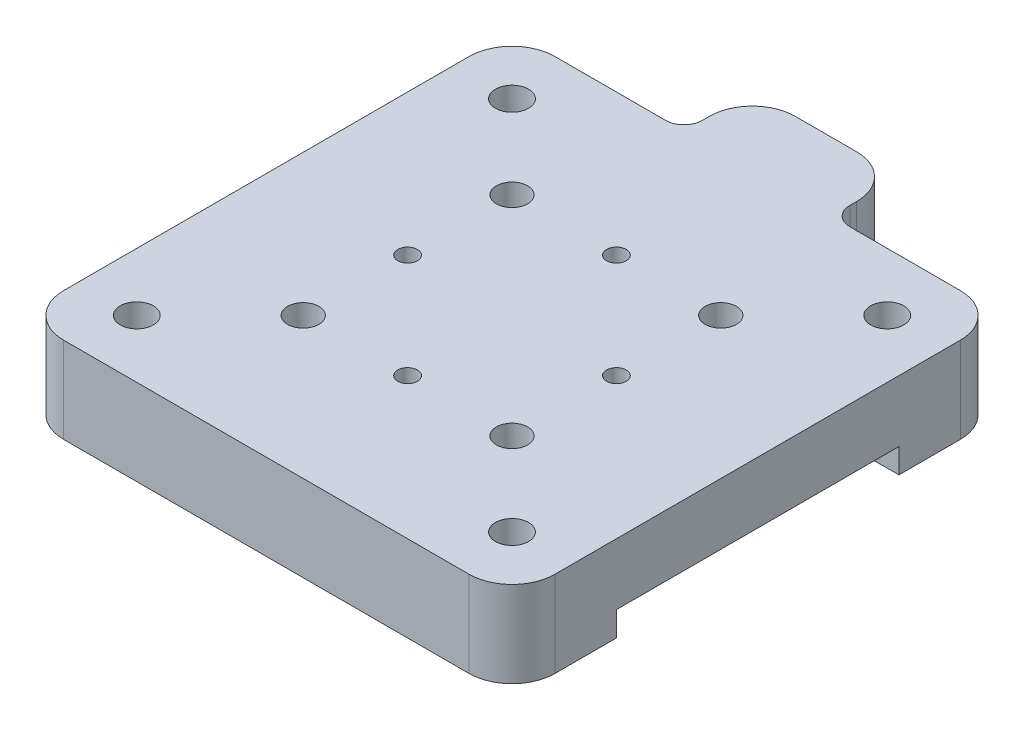
SolidWorks part; units mm, degrees
ref_plane "Front Plane" through (0, 0, 0) normal (0, 0, 1) x (1, 0, 0)
ref_plane "Top Plane" through (0, 0, 0) normal (0, 1, 0) x (1, 0, 0)
ref_plane "Right Plane" through (0, 0, 0) normal (1, 0, 0) x (0, 0, -1)
sketch "Sketch1" plane through (0, 0, 0) normal (0, 1, 0) x (1, 0, 0)
  line L3 (0, 40) -> (40, 40)
  line L4 (40, 0) -> (40, 40)
  line L5 (40, 40) -> (-40, 40)
  line L6 (40, 40) -> (40, -40)
  line L7 (40, -40) -> (-40, -40)
  line L8 (-40, 40) -> (-40, -40)
  line L12 (0, 40) -> (-30.55, 40)
  circle A5 centre (-30.55, 30.55) radius 2.7
  circle A6 centre (30.55, 30.55) radius 2.7
  circle A7 centre (30.55, -30.55) radius 2.7
  circle A8 centre (-30.55, -30.55) radius 2.7
extrude "Boss-Extrude1" add sketch "Sketch1" along normal blind 10 contours L5 L8 L7 L6 L4 L3 A8 A7 A6 A5 region at (0, 0, 0)
sketch "Sketch3" plane through (-40, 0, 0) normal (-1, 0, 0) x (0, 0, 1)
  line L1 (-40, 0) -> (-23, 0)
  line L12 (-40, 0) -> (-40, -4)
  line L13 (-40, -4) -> (-23, -4)
  line L14 (-23, 0) -> (-23, -4)
  line L15 (40, 0) -> (23, 0)
  line L16 (40, 0) -> (40, -4)
  line L17 (40, -4) -> (23, -4)
  line L18 (23, 0) -> (23, -4)
extrude "Boss-Extrude2" add sketch "Sketch3" against normal up to surface (80 mm away) up to face at (40, 5, 0)
sketch "Sketch4" plane through (0, 10, 0) normal (0, 1, 0) x (1, 0, 0)
  circle A0 centre (30.55, -30.55) radius 2.7 construction
  circle A1 centre (-30.55, -30.55) radius 2.7 construction
  circle A2 centre (-30.55, 30.55) radius 2.7 construction
  circle A3 centre (30.55, 30.55) radius 2.7 construction
  circle A4 centre (30.55, -30.55) radius 2.7
  circle A5 centre (-30.55, -30.55) radius 2.7
  circle A6 centre (-30.55, 30.55) radius 2.7
  circle A7 centre (30.55, 30.55) radius 2.7
extrude "Cut-Extrude1" cut sketch "Sketch4" against normal blind 36
sketch "Sketch5" plane through (0, -4, 0) normal (0, -1, 0) x (1, 0, 0)
  circle A0 centre (-30.55, -30.55) radius 4.7
  circle A1 centre (-30.55, 30.55) radius 4.7
  circle A2 centre (30.55, 30.55) radius 4.7
  circle A3 centre (30.55, -30.55) radius 4.7
  circle A4 centre (30.55, -30.55) radius 2.7 construction
  circle A5 centre (30.55, 30.55) radius 2.7 construction
  circle A6 centre (-30.55, 30.55) radius 2.7 construction
  circle A7 centre (-30.55, -30.55) radius 2.7 construction
  circle A8 centre (30.55, -30.55) radius 2.7
  circle A9 centre (30.55, 30.55) radius 2.7
  circle A10 centre (-30.55, 30.55) radius 2.7
  circle A11 centre (-30.55, -30.55) radius 2.7
extrude "Boss-Extrude3" add sketch "Sketch5" along normal blind 3
chamfer "Chamfer1" distance 1 angle 45 4 edges at (30.55, -7, -35.25) (30.55, -7, 25.85) (-30.55, -7, 25.85) (-30.55, -7, -35.25)
fillet "Fillet2" radius 7 4 edges at (40, 3, 40) (-40, 3, 40) (40, 3, -40) (-40, 3, -40)
sketch "Sketch6" plane through (0, 0, 0) normal (0, -1, 0) x (1, 0, 0)
  circle A0 centre (0, 0) radius 12.5
extrude "Cut-Extrude2" cut sketch "Sketch6" against normal blind 2
chamfer "Chamfer2" distance 2 angle 45 1 edges at (0, 0, -12.5)
sketch "Sketch7" plane through (0, 2, 0) normal (0, -1, 0) x (1, 0, 0)
  circle A0 centre (0, 0) radius 3.25
extrude "Cut-Extrude3" cut sketch "Sketch7" against normal blind 19
sketch "Sketch8" plane through (0, 10, 0) normal (0, 1, 0) x (1, 0, 0)
  circle A0 centre (0, 0) radius 32.55
extrude "Cut-Extrude4" cut sketch "Sketch8" against normal blind 2
sketch "Sketch9" plane through (0, 8, 0) normal (0, 1, 0) x (1, 0, 0)
  circle A0 centre (0, 0) radius 32.55
extrude "Boss-Extrude4" add sketch "Sketch9" along normal up to surface and the other way up to surface up to face at (0, 10, 32.55) other way up to face at (0, 0, 14.5)
sketch "Sketch10" plane through (0, -4, 0) normal (0, -1, 0) x (1, 0, 0)
  line L0 (33, -40) -> (-33, -40) construction
  line L1 (0, -40) -> (12, -40)
  line L2 (0, -40) -> (0, -23)
  line L3 (0, -23) -> (12, -23)
  line L4 (12, -40) -> (12, -23)
  line L5 (40, -23) -> (-40, -23) construction
  line L7 (0, -40) -> (-12, -40)
  line L8 (0, -40) -> (0, -23)
  line L9 (0, -23) -> (-12, -23)
  line L10 (-12, -40) -> (-12, -23)
  line M2 (-33, -40) -> (33, -40)
  line M5 (40, -23) -> (-40, -23)
extrude "Boss-Extrude5" add sketch "Sketch10" along normal blind 3 contours L4 L2 M2 M5 | L10 L2 M2 M5 region at (6, -4, -31.5) region at (-6, -4, -31.5)
sketch "Sketch11" plane through (0, -7, 0) normal (0, -1, 0) x (1, 0, 0)
  line L0 (9.8743, -23) -> (1.2, -23)
  line L1 (1.2, -23) -> (1.2, -32.2366)
  line L2 (-1.2, -32.2366) -> (-1.2, -23)
  line L3 (-1.2, -23) -> (-9.9087, -23)
  line L5 (-9.9087, -51.1281) -> (-1.2, -51.1281)
  line L7 (1.2, -47.7634) -> (1.2, -51.1281)
  line L9 (-1.2, -47.7634) -> (-1.2, -51.1281)
  line L10 (1.2, -51.1281) -> (9.8743, -51.1281)
  line L12 (12, -23) -> (9.8743, -23)
  line L13 (12, -23) -> (12, -51.1281)
  line L14 (12, -51.1281) -> (9.8743, -51.1281)
  line L16 (-12, -23) -> (-9.9087, -23)
  line L17 (-12, -23) -> (-12, -51.1281)
  line L18 (-12, -51.1281) -> (-9.9087, -51.1281)
  circle A0 centre (0, -40) radius 4.5
  arc A1 (1.2, -32.2366) -> (2.6244, -34.4934) centre (3.7, -32.2366) ccw
  arc A2 (-2.6244, -34.4934) -> (-2.6244, -45.5066) centre (0, -40) ccw
  arc A3 (-2.6244, -34.4934) -> (-1.2, -32.2366) centre (-3.7, -32.2366) ccw
  arc A4 (2.6244, -45.5066) -> (2.6244, -34.4934) centre (0, -40) ccw
  arc A5 (-2.6244, -45.5066) -> (-1.2, -47.7634) centre (-3.7, -47.7634) cw
  arc A6 (1.2, -47.7634) -> (2.6244, -45.5066) centre (3.7, -47.7634) cw
  dimension "D1" = 2.5
extrude "Boss-Extrude6" add sketch "Sketch11" along normal blind 7
sketch "Sketch12" plane through (0, -7, 0) normal (0, 1, 0) x (1, 0, 0)
  line L1 (-12, 51.1281) -> (12, 51.1281)
  line L2 (-12, 51.1281) -> (-12, 40)
  line L3 (-12, 40) -> (12, 40)
  line L4 (12, 51.1281) -> (12, 40)
extrude "Boss-Extrude7" add sketch "Sketch12" along normal up to surface (17 mm away) up to face at (-30.55, 10, 33.25)
sketch "Sketch13" plane through (0, 10, 0) normal (0, 1, 0) x (1, 0, 0)
  line L0 (-17, 17) -> (-17, -17)
  line L1 (-23, 23) -> (23, 23)
  line L3 (-23, 23) -> (-23, -23)
  line L4 (-40, -23) -> (40, -23)
  line L5 (-40, 23) -> (-40, -23)
  line L6 (40, 23) -> (-40, 23)
  line L7 (40, -23) -> (40, 23)
  line L9 (-40, 23) -> (-40, -23)
  line L14 (-23, 23) -> (-23, -23)
  line L15 (-23, -23) -> (23, -23)
  line L16 (23, 23) -> (23, -23)
  line L17 (-17, -17) -> (17, -17)
  line L18 (17, 17) -> (17, -17)
  line L19 (-17, 17) -> (17, 17)
  circle A0 centre (-17, 17) radius 2.55
  circle A1 centre (17, 17) radius 2.55
  circle A2 centre (17, -17) radius 2.55
  circle A3 centre (-17, -17) radius 2.55
  circle A4 centre (-17, 0) radius 1.6
  circle A5 centre (17, 0) radius 1.6
  circle A6 centre (0, 17) radius 1.6
  circle A7 centre (0, -17) radius 1.6
  dimension "D2" = 6
  dimension "D1" = 0
extrude "Cut-Extrude5" cut sketch "Sketch13" against normal blind 30 contours L19 A0 L0 | L0 A0 L19 | L19 A6 | L19 A6 | L18 A1 L19 | L19 A1 L18 | L18 A5 | L18 A5 | L17 A2 L18 | L18 A2 L17 | L17 A7 | L17 A7 | L0 A3 L17 | L17 A3 L0 | L0 A4 | L0 A4 region at (-15.9177, 10, -15.9177) region at (-17.3608, 10, -17.3608) region at (-16.3209, 10, 0) region at (-17.6791, 10, 0) region at (0, 10, -17.6791) region at (0, 10, -16.3209) region at (-15.9177, 10, 15.9177) region at (-17.3608, 10, 17.3608) region at (17.3608, 10, -17.3608) region at (15.9177, 10, -15.9177) region at (0, 10, 16.3209) region at (0, 10, 17.6791) region at (17.6791, 10, 0) region at (16.3209, 10, 0) region at (15.9177, 10, 15.9177) region at (17.3608, 10, 17.3608)
fillet "Fillet3" radius 7 2 edges at (-12, -2, -51.1281) (12, -2, -51.1281)
fillet "Fillet4" radius 3 4 edges at (-12, 3, -40) (12, 3, -40) (12, -4, -31.5) (-12, -4, -31.5)
